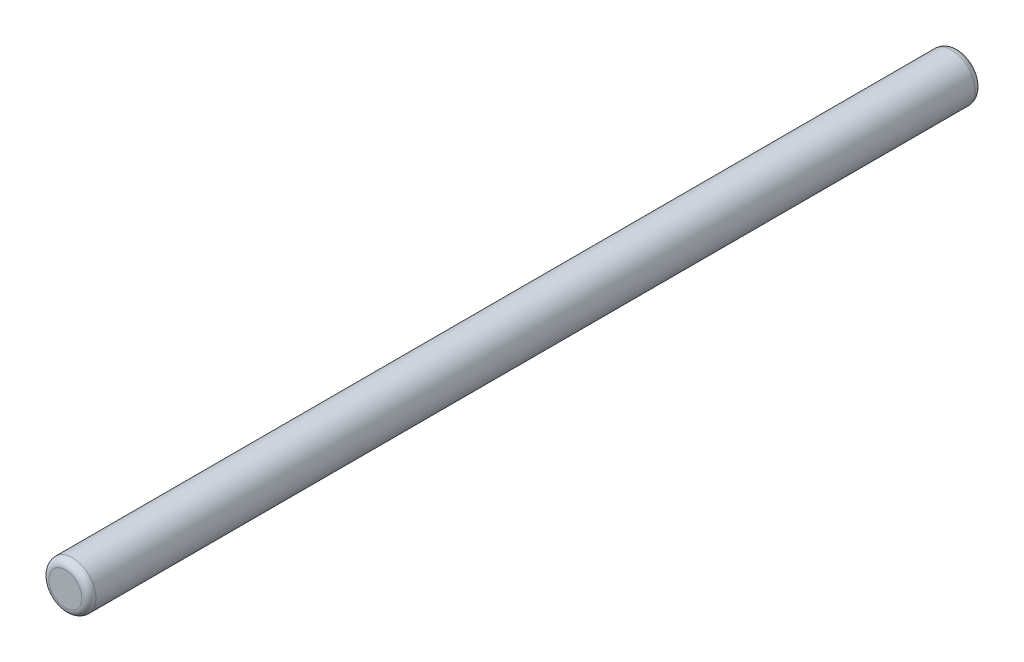
SolidWorks part; units mm, degrees
note: '?' marks a value the reader was unsure of.
ref_plane "Face" through (0, 0, 0) normal (0, 0, 1) x (1, 0, 0)
ref_plane "Dessus" through (0, 0, 0) normal (0, 1, 0) x (1, 0, 0)
ref_plane "Droite" through (0, 0, 0) normal (1, 0, 0) x (0, 0, -1)
ref_plane "Plan1" through (0, 0, 1.65) normal (0, 0, 1) x (1, 0, 0)
ref_axis "Axe1" through (0, 0, 0) along (0, 0, 1)?
ref_plane "Plan2" through (0, 0, 41) normal (0, 0, 1) x (1, 0, 0)
sketch "Esquisse1" plane through (0, 0, 0) normal (0, 0, 1) x (1, 0, 0)
  circle A0 centre (0, 0) radius 1
extrude "Base-Extrusion" add sketch "Esquisse1" along normal blind 38
fillet "Congé1" radius 0.3
